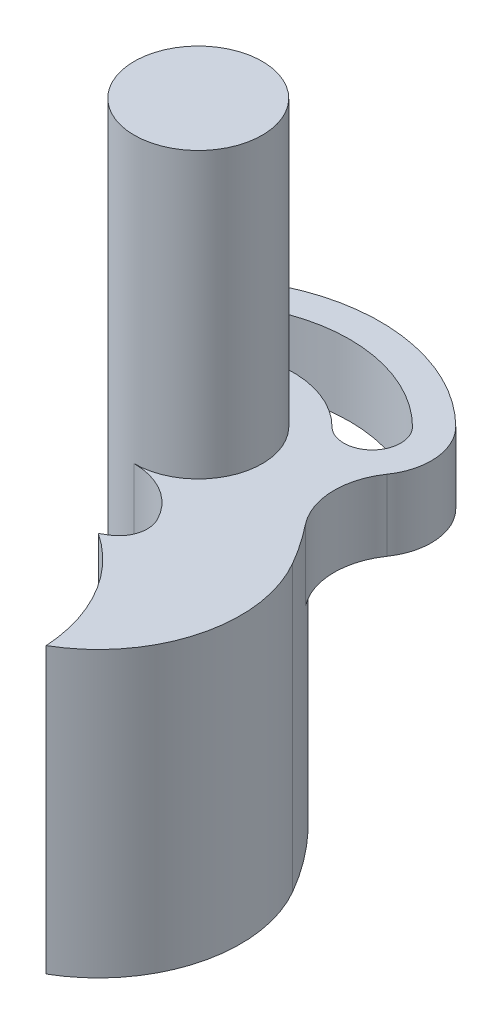
SolidWorks part; units mm, degrees
ref_plane "Alzado" through (0, 0, 0) normal (0, 0, 1) x (1, 0, 0)
ref_plane "Planta" through (0, 0, 0) normal (0, 1, 0) x (1, 0, 0)
ref_plane "Vista lateral" through (0, 0, 0) normal (1, 0, 0) x (0, 0, -1)
sketch "Croquis1" plane through (0, 0, 0) normal (0, 1, 0) x (1, 0, 0)
  line L0 (0, 7.5) -> (-6.4952, -3.75) construction
  line L1 (-6.4952, -3.75) -> (6.4952, -3.75) construction
  line L2 (6.4952, -3.75) -> (0, 7.5) construction
  line L3 (-6.4952, 3.75) -> (6.4952, 3.75) construction
  line L4 (6.4952, 3.75) -> (0, -7.5) construction
  line L5 (0, -7.5) -> (-6.4952, 3.75) construction
  line L6 (2.9801, 7.494) -> (7.9801, -1.1662)
  line L7 (2.9801, 7.494) -> (11.6403, 12.494)
  line L8 (11.6403, 12.494) -> (16.6403, 3.8338)
  line L9 (16.6403, 3.8338) -> (7.9801, -1.1662)
  line L10 (0, 17.5) -> (0, 7.5) construction
  line L11 (0, 0) -> (0, 7.5) construction
  circle A0 centre (0, 0) radius 7.5 construction
  circle A1 centre (0, 0) radius 20
  arc A5 (0, 13) -> (4.7121, 8.494) centre (0, 8.2832) cw
  circle A7 centre (0, 17.5) radius 4.5
  circle A8 centre (0, 17.5) radius 10 construction
  arc A10 (11.6403, 12.494) -> (1.9923, 21.5349) centre (-8.0991, 1.0975) ccw
  arc A11 (2.9801, 7.494) -> (7.9801, -1.1662) centre (-3.2476, -1.875) cw
  dimension "D1" = 15
  dimension "D2" = 40
  dimension "D3" = 10
  dimension "D4" = 2
  dimension "D5" = 9
  dimension "D6" = 10
  dimension "D7" = 10
extrude "Saliente-Extruir1" add sketch "Croquis1" against normal blind 20 contours L9 L8 L7 L6 | L7 A10 A7 | A7 | A1 A7 | A1 A10 A7 region at (10.1466, 0, -5.8581) region at (6.4716, 0, -13.7898) region at (0, 0, -16.7859) region at (4.2097, 0, -20.0044) region at (0, 0, -20.7389)
fillet "Redondeo1" radius 10 1 edges at (16.6403, -10, -3.8338)
extrude "Saliente-Extruir2" add sketch "Croquis1<4>" along normal blind 20 contours A7
sketch "Croquis1<4>" plane through (0, 0, 0) normal (0, 1, 0) x (1, 0, 0) same geometry as "Croquis1"
sketch "Croquis2" plane through (0, 0, 0) normal (0, 1, 0) x (1, 0, 0)
  line L0 (0, 17.5) -> (6.1168, 23.6168) construction
  line L2 (0, 17.5) -> (-4.9617, 24.5861) construction
  line L3 (0, 17.5) -> (10.0052, 17.5) construction
  line L4 (10.0807, 19.829) -> (8.927, -15.7718) construction
  circle A0 centre (0, 17.5) radius 8.6505 construction
  arc A7 (-4.9617, 24.5861) -> (6.1168, 23.6168) centre (0, 17.5) cw construction
  arc A16 (7.5311, 25.0311) -> (-6.1089, 26.2244) centre (0, 17.5) ccw
  arc A17 (4.7026, 22.2026) -> (-3.8146, 22.9478) centre (0, 17.5) ccw
  arc A18 (4.7026, 22.2026) -> (7.5311, 25.0311) centre (6.1168, 23.6168) ccw
  arc A19 (-6.1089, 26.2244) -> (-3.8146, 22.9478) centre (-4.9617, 24.5861) ccw
  arc A21 (-4.9617, 24.5861) -> (6.1168, 23.6168) centre (0, 17.5) cw construction
  arc A22 (9.0517, 26.5517) -> (-7.3424, 27.986) centre (0, 17.5) ccw
  arc A23 (3.182, 20.682) -> (-2.5811, 21.1862) centre (0, 17.5) ccw
  arc A24 (3.182, 20.682) -> (9.0517, 26.5517) centre (6.1168, 23.6168) ccw
  arc A25 (-7.3424, 27.986) -> (-2.5811, 21.1862) centre (-4.9617, 24.5861) ccw
  circle A26 centre (0, 17.5) radius 4.5 construction
  point P14 (0.7539, 26.1176)
  point P25 (0.7539, 26.1176)
  dimension "D1" = 2
  dimension "D2" = 125
  dimension "D3" = 45
extrude "Saliente-Extruir4" add sketch "Croquis2" against normal blind 5
fillet "Redondeo4" radius 5 2 edges at (-2.5811, -2.5, -21.1862) (5.2786, -2.5, -19.5519)
fillet "Redondeo5" radius 2 1 edges at (4.7121, -10, -8.494)
